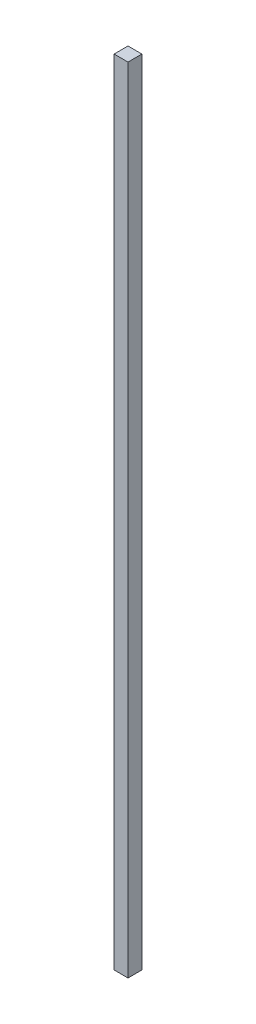
SolidWorks part; units mm, degrees
ref_plane "Front Plane" through (0, 0, 0) normal (0, 0, 1) x (1, 0, 0)
ref_plane "Top Plane" through (0, 0, 0) normal (0, 1, 0) x (1, 0, 0)
ref_plane "Right Plane" through (0, 0, 0) normal (1, 0, 0) x (0, 0, -1)
sketch "Sketch1" plane through (0, 0, 0) normal (0, 1, 0) x (1, 0, 0)
  line L1 (0, 0) -> (25.4, 0)
  line L2 (0, 0) -> (0, 25.4)
  line L3 (0, 25.4) -> (25.4, 25.4)
  line L4 (25.4, 0) -> (25.4, 25.4)
  dimension "D1" = 25.4
  dimension "D2" = 25.4
extrude "Boss-Extrude1" add sketch "Sketch1" along normal blind 1447.8
